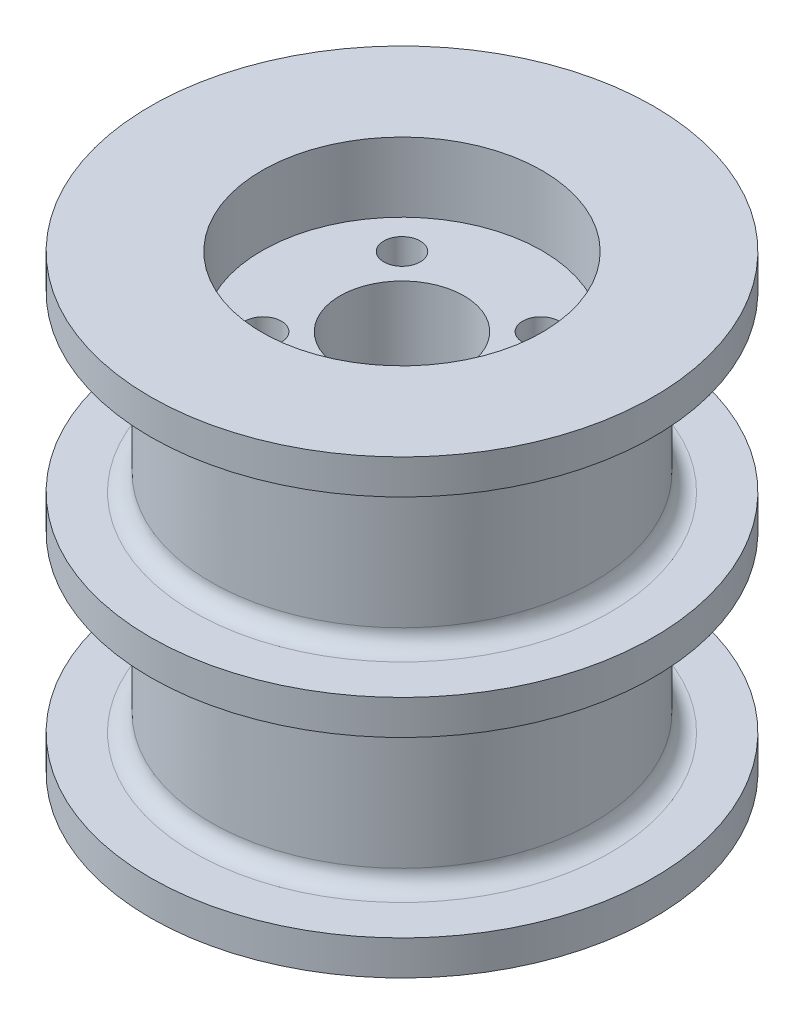
SolidWorks part; units mm, degrees
material "ABS"
ref_plane "前视基准面" through (0, 0, 0) normal (0, 0, 1) x (1, 0, 0)
ref_plane "上视基准面" through (0, 0, 0) normal (0, 1, 0) x (1, 0, 0)
ref_plane "右视基准面" through (0, 0, 0) normal (1, 0, 0) x (0, 0, -1)
other "Configuration Table"
sketch "草图1" plane through (0, 0, 0) normal (1, 0, 0) x (0, 0, -1)
  line L0 (0, 0) -> (0, 55.9155) construction
  line L1 (-7.15, 44) -> (-16.15, 44)
  line L2 (-16.15, 44) -> (-16.15, 52)
  line L3 (-16.15, 52) -> (-29, 52)
  line L4 (-29, 52) -> (-29, 48)
  line L5 (-29, 48) -> (-22, 48)
  line L6 (-22, 48) -> (-22, 28)
  line L7 (-22, 28) -> (-29, 28)
  line L8 (-29, 28) -> (-29, 24)
  line L9 (-29, 24) -> (-22, 24)
  line L10 (-22, 24) -> (-22, 4)
  line L11 (-22, 4) -> (-29, 4)
  line L12 (-29, 4) -> (-29, 0)
  line L13 (-29, 0) -> (-16.15, 0)
  line L14 (0, 0) -> (0, 44) construction
  line L15 (-16.15, 0) -> (-16.15, 8)
  line L16 (-16.15, 8) -> (-7.15, 8)
  line L17 (-16.15, 0) -> (0, 0) construction
  line L18 (-7.15, 44) -> (-7.15, 8)
  dimension "D1" = 4
  dimension "D2" = 4
  dimension "D3" = 4
  dimension "D4" = 20
  dimension "D7" = 29
  dimension "D8" = 20
  dimension "D10" = 22
  dimension "D11" = 16.15
  dimension "D12" = 8
  dimension "D13" = 8
  dimension "D14" = 16.15
  dimension "D15" = 7.15
  dimension "D16" = 16.15
revolve "旋转1" add sketch "草图1" angle 360 about L0
sketch "草图2" plane through (0, 44, 0) normal (0, 1, 0) x (1, 0, 0)
  line L1 (8, -8) -> (-8, -8) construction
  line L2 (8, -8) -> (8, 8) construction
  line L3 (8, 8) -> (-8, 8) construction
  line L4 (-8, -8) -> (-8, 8) construction
  line L5 (8, -8) -> (-8, 8) construction
  line L6 (8, 8) -> (-8, -8) construction
  circle A0 centre (-8, 8) radius 2.1
  circle A1 centre (8, 8) radius 2.1
  circle A2 centre (8, -8) radius 2.1
  circle A3 centre (-8, -8) radius 2.1
  point P0 (0, 0)
  dimension "D2" = 4.2
  dimension "D1" = 16
extrude "切除-拉伸1" cut sketch "草图2" against normal through all
fillet "圆角1" radius 2 4 edges at (0, 24, -22) (0, 4, -22) (0, 48, -22) (0, 28, -22)
ref_axis "基准轴2" through (0, 22, 0) along (0, -1, 0)
